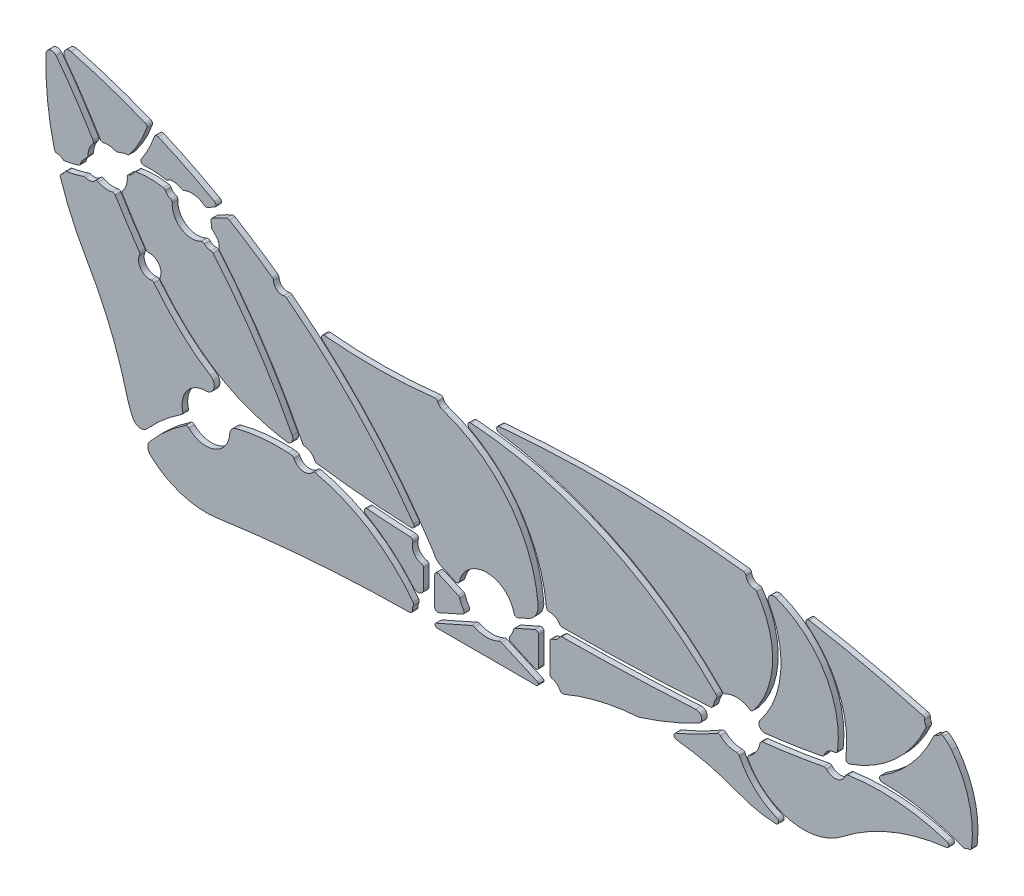
SolidWorks part; units mm, degrees
material "ｴﾎﾟｷｼ樹脂(充填剤なし)"
ref_plane "正面" through (0, 0, 0) normal (0, 0, 1) x (1, 0, 0)
ref_plane "平面" through (0, 0, 0) normal (0, 1, 0) x (1, 0, 0)
ref_plane "右側面" through (0, 0, 0) normal (1, 0, 0) x (0, 0, -1)
sketch "ｽｹｯﾁ1" plane through (0, 0, 0) normal (0, 0, 1) x (1, 0, 0)
  line L1 (22.5, 0.101) -> (22.5, -10.101)
  line L2 (22.5, 0.101) -> (22.5, -10.101)
  line L3 (-22.5, -6.4126) -> (-22.5, 0.101)
  line L4 (-22.5, -6.4126) -> (-22.5, 0.101)
  line L6 (11.119, 1.5832) -> (14.7807, 3.2107)
  line L7 (-17.0939, -10.9558) -> (-8.626, -7.1923)
  line L8 (-18.5, 0.042) -> (-18.5, -10.042)
  line L9 (-10.1663, -2.1231) -> (-17.0939, 0.9558)
  line L10 (-17.0939, -10.9558) -> (-8.626, -7.1923)
  line L11 (-18.5, 0.042) -> (-18.5, -10.042)
  line L12 (-10.1663, -2.1231) -> (-17.0939, 0.9558)
  line L13 (8.626, -7.1923) -> (17.0939, -10.9558)
  line L14 (17.0939, 0.9558) -> (10.1663, -2.1231)
  line L15 (18.5, -10.042) -> (18.5, 0.042)
  line L16 (8.626, -7.1923) -> (17.0939, -10.9558)
  line L17 (17.0939, 0.9558) -> (10.1663, -2.1231)
  line L18 (18.5, -10.042) -> (18.5, 0.042)
  line L19 (-16.2024, 3.8425) -> (-11.119, 1.5832)
  line L20 (11.119, 1.5832) -> (14.7807, 3.2107)
  line L21 (-16.2024, 3.8425) -> (-11.119, 1.5832)
  line L23 (-17.5, -16) -> (17.5, -16)
  line L24 (-5.2366, -8.9688) -> (-17.9339, -14.6121)
  line L25 (17.9339, -14.6121) -> (5.2366, -8.9688)
  line L26 (-17.5, -16) -> (17.5, -16)
  line L27 (-5.2366, -8.9688) -> (-17.9339, -14.6121)
  line L28 (17.9339, -14.6121) -> (5.2366, -8.9688)
  arc A26 (83.2113, 1.2758) -> (89.0603, -0.9998) centre (89, 7.5) ccw
  arc A27 (89.967, -1.5631) -> (89.0603, -0.9998) centre (89.0674, -1.9998) ccw
  arc A28 (89.967, -1.5631) -> (103.3566, -14.0607) centre (112.8701, 9.5532) ccw
  arc A29 (102.9573, -15.9879) -> (103.3566, -14.0607) centre (102.9829, -14.9883) ccw
  arc A30 (90.1176, -13.3365) -> (102.9573, -15.9879) centre (103.9017, 21) ccw
  arc A31 (90.1176, -13.3365) -> (67.6378, -7.8134) centre (59.3978, -89.8605) ccw
  arc A32 (67.3468, -5.898) -> (67.6378, -7.8134) centre (67.7378, -6.8184) ccw
  arc A33 (67.3468, -5.898) -> (82.0317, 1.4104) centre (13.9413, 119.818) ccw
  arc A34 (83.2113, 1.2758) -> (82.0317, 1.4104) centre (82.5302, 0.5435) ccw
  arc A35 (83.2113, 1.2758) -> (89.0603, -0.9998) centre (89, 7.5) ccw
  arc A36 (89.967, -1.5631) -> (89.0603, -0.9998) centre (89.0674, -1.9998) ccw
  arc A37 (89.967, -1.5631) -> (103.3566, -14.0607) centre (112.8701, 9.5532) ccw
  arc A38 (102.9573, -15.9879) -> (103.3566, -14.0607) centre (102.9829, -14.9883) ccw
  arc A39 (90.1176, -13.3365) -> (102.9573, -15.9879) centre (103.9017, 21) ccw
  arc A40 (90.1176, -13.3365) -> (67.6378, -7.8134) centre (59.3978, -89.8605) ccw
  arc A41 (67.3468, -5.898) -> (67.6378, -7.8134) centre (67.7378, -6.8184) ccw
  arc A42 (67.3468, -5.898) -> (82.0317, 1.4104) centre (13.9413, 119.818) ccw
  arc A43 (83.2113, 1.2758) -> (82.0317, 1.4104) centre (82.5302, 0.5435) ccw
  arc A45 (129.2172, 15.4989) -> (156.4002, 40.1644) centre (114.0417, 59.5347) ccw
  arc A46 (127.9008, 16.5808) -> (129.2172, 15.4989) centre (128.8914, 16.4443) ccw
  arc A47 (127.9008, 16.5808) -> (114.0595, 50.8962) centre (91.0356, 21.6602) ccw
  arc A48 (163.9203, 8.9775) -> (128.5572, 11.8079) centre (140.2604, -64.3004) ccw
  arc A49 (163.7257, 7.0322) -> (163.9203, 8.9775) centre (163.613, 8.0259) ccw
  arc A50 (163.7257, 7.0322) -> (126.7209, -8.1253) centre (172, -65.9175) ccw
  arc A51 (93.0844, -1.0722) -> (126.7209, -8.1253) centre (112.8701, 9.5532) ccw
  arc A52 (93.4427, 0.2535) -> (93.0844, -1.0722) centre (93.9654, -0.5991) ccw
  arc A53 (93.4427, 0.2535) -> (97.3718, 6.0294) centre (89, 7.5) ccw
  arc A54 (98.2474, 6.8503) -> (97.3718, 6.0294) centre (98.3567, 5.8563) ccw
  arc A55 (98.2474, 6.8503) -> (120.0633, 10.1693) centre (69.0994, 271.8045) ccw
  arc A56 (121.0036, 9.8502) -> (120.0633, 10.1693) centre (120.2545, 9.1877) ccw
  arc A57 (121.0036, 9.8502) -> (127.7673, 11.1556) centre (124, 12.5) ccw
  arc A58 (128.5572, 11.8079) -> (127.7673, 11.1556) centre (128.7091, 10.8195) ccw
  arc A59 (163.9203, 8.9775) -> (128.5572, 11.8079) centre (140.2604, -64.3004) ccw
  arc A60 (163.7257, 7.0322) -> (163.9203, 8.9775) centre (163.613, 8.0259) ccw
  arc A61 (163.7257, 7.0322) -> (126.7209, -8.1253) centre (172, -65.9175) ccw
  arc A62 (93.0844, -1.0722) -> (126.7209, -8.1253) centre (112.8701, 9.5532) ccw
  arc A63 (93.4427, 0.2535) -> (93.0844, -1.0722) centre (93.9654, -0.5991) ccw
  arc A64 (93.4427, 0.2535) -> (97.3718, 6.0294) centre (89, 7.5) ccw
  arc A65 (98.2474, 6.8503) -> (97.3718, 6.0294) centre (98.3567, 5.8563) ccw
  arc A66 (98.2474, 6.8503) -> (120.0633, 10.1693) centre (69.0994, 271.8045) ccw
  arc A67 (121.0036, 9.8502) -> (120.0633, 10.1693) centre (120.2545, 9.1877) ccw
  arc A68 (121.0036, 9.8502) -> (127.7673, 11.1556) centre (124, 12.5) ccw
  arc A69 (128.5572, 11.8079) -> (127.7673, 11.1556) centre (128.7091, 10.8195) ccw
  arc A70 (114.85, 52.6669) -> (114.0595, 50.8962) centre (114.6782, 51.6818) ccw
  arc A71 (155.2686, 43.5545) -> (114.85, 52.6669) centre (42.29, -363.3692) ccw
  arc A72 (156.0008, 42.5682) -> (155.2686, 43.5545) centre (155.001, 42.5909) ccw
  arc A73 (156.0008, 42.5682) -> (156.3681, 41.0602) centre (159, 42.5) ccw
  arc A74 (156.4002, 40.1644) -> (156.3681, 41.0602) centre (155.4908, 40.5803) ccw
  arc A75 (129.2172, 15.4989) -> (156.4002, 40.1644) centre (114.0417, 59.5347) ccw
  arc A76 (127.9008, 16.5808) -> (129.2172, 15.4989) centre (128.8914, 16.4443) ccw
  arc A77 (127.9008, 16.5808) -> (114.0595, 50.8962) centre (91.0356, 21.6602) ccw
  arc A78 (114.85, 52.6669) -> (114.0595, 50.8962) centre (114.6782, 51.6818) ccw
  arc A79 (155.2686, 43.5545) -> (114.85, 52.6669) centre (42.29, -363.3692) ccw
  arc A80 (156.0008, 42.5682) -> (155.2686, 43.5545) centre (155.001, 42.5909) ccw
  arc A81 (156.0008, 42.5682) -> (156.3681, 41.0602) centre (159, 42.5) ccw
  arc A82 (156.4002, 40.1644) -> (156.3681, 41.0602) centre (155.4908, 40.5803) ccw
  arc A83 (97.4246, 13.2154) -> (99.214, 9.978) centre (98.9855, 11.9649) ccw
  arc A84 (97.4246, 13.2154) -> (100.5051, 50.879) centre (71.0713, 34.3286) ccw
  arc A85 (93.5868, 14.6562) -> (85.0963, 15.0506) centre (89, 7.5) ccw
  arc A86 (171.786, 10.4924) -> (170.5639, 10.1339) centre (172, 7.5) ccw
  arc A87 (169.717, 10.0822) -> (170.5639, 10.1339) centre (170.0852, 11.0119) ccw
  arc A88 (169.717, 10.0822) -> (140.9263, 15.6997) centre (140.2604, -64.3004) ccw
  arc A89 (140.4029, 17.5466) -> (140.9263, 15.6997) centre (140.9346, 16.6997) ccw
  arc A90 (140.4029, 17.5466) -> (159.198, 39.0695) centre (114.0417, 59.5347) ccw
  arc A91 (159.8316, 39.6176) -> (159.198, 39.0695) centre (160.1088, 38.6568) ccw
  arc A92 (159.8316, 39.6176) -> (161.317, 40.5944) centre (159, 42.5) ccw
  arc A93 (162.6526, 40.7855) -> (161.317, 40.5944) centre (162.0894, 39.9592) ccw
  arc A94 (165.6353, 37.9447) -> (162.6526, 40.7855) centre (155.4945, 30.2837) ccw
  arc A95 (172.7066, 11.3632) -> (165.6353, 37.9447) centre (136.5587, 15.9784) ccw
  arc A96 (171.786, 10.4924) -> (172.7066, 11.3632) centre (171.7146, 11.4898) ccw
  arc A97 (171.786, 10.4924) -> (170.5639, 10.1339) centre (172, 7.5) ccw
  arc A98 (169.717, 10.0822) -> (170.5639, 10.1339) centre (170.0852, 11.0119) ccw
  arc A99 (169.717, 10.0822) -> (140.9263, 15.6997) centre (140.2604, -64.3004) ccw
  arc A100 (140.4029, 17.5466) -> (140.9263, 15.6997) centre (140.9346, 16.6997) ccw
  arc A101 (140.4029, 17.5466) -> (159.198, 39.0695) centre (114.0417, 59.5347) ccw
  arc A102 (159.8316, 39.6176) -> (159.198, 39.0695) centre (160.1088, 38.6568) ccw
  arc A103 (159.8316, 39.6176) -> (161.317, 40.5944) centre (159, 42.5) ccw
  arc A104 (162.6526, 40.7855) -> (161.317, 40.5944) centre (162.0894, 39.9592) ccw
  arc A105 (165.6353, 37.9447) -> (162.6526, 40.7855) centre (155.4945, 30.2837) ccw
  arc A106 (172.7066, 11.3632) -> (165.6353, 37.9447) centre (136.5587, 15.9784) ccw
  arc A107 (171.786, 10.4924) -> (172.7066, 11.3632) centre (171.7146, 11.4898) ccw
  arc A108 (83.9236, 15.238) -> (85.0963, 15.0506) centre (84.637, 15.9389) ccw
  arc A109 (83.9236, 15.238) -> (4.4224, 55.2639) centre (-14.6672, -81.6202) ccw
  arc A110 (4.471, 57.2503) -> (4.4224, 55.2639) centre (4.5606, 56.2543) ccw
  arc A111 (91.4838, 56.0721) -> (4.471, 57.2503) centre (42.29, -363.3692) ccw
  arc A112 (92.3587, 55.2099) -> (91.4838, 56.0721) centre (91.3673, 55.0789) ccw
  arc A113 (92.3587, 55.2099) -> (95.319, 52.6028) centre (95.3328, 55.6027) ccw
  arc A114 (96.1287, 52.1831) -> (95.319, 52.6028) centre (95.3143, 51.6028) ccw
  arc A115 (94.9009, 14.8656) -> (96.1287, 52.1831) centre (71.0713, 34.3286) ccw
  arc A116 (93.5868, 14.6562) -> (94.9009, 14.8656) centre (94.1264, 15.4981) ccw
  arc A117 (93.5868, 14.6562) -> (85.0963, 15.0506) centre (89, 7.5) ccw
  arc A118 (83.9236, 15.238) -> (85.0963, 15.0506) centre (84.637, 15.9389) ccw
  arc A119 (83.9236, 15.238) -> (4.4224, 55.2639) centre (-14.6672, -81.6202) ccw
  arc A120 (4.471, 57.2503) -> (4.4224, 55.2639) centre (4.5606, 56.2543) ccw
  arc A121 (91.4838, 56.0721) -> (4.471, 57.2503) centre (42.29, -363.3692) ccw
  arc A122 (92.3587, 55.2099) -> (91.4838, 56.0721) centre (91.3673, 55.0789) ccw
  arc A123 (92.3587, 55.2099) -> (95.319, 52.6028) centre (95.3328, 55.6027) ccw
  arc A124 (96.1287, 52.1831) -> (95.319, 52.6028) centre (95.3143, 51.6028) ccw
  arc A125 (94.9009, 14.8656) -> (96.1287, 52.1831) centre (71.0713, 34.3286) ccw
  arc A126 (93.5868, 14.6562) -> (94.9009, 14.8656) centre (94.1264, 15.4981) ccw
  arc A127 (81.6673, 13.2539) -> (-5.6096, 53.2849) centre (-14.6672, -81.6202) ccw
  arc A128 (81.8017, 12.0204) -> (81.6673, 13.2539) centre (80.9548, 12.5522) ccw
  arc A129 (81.8017, 12.0204) -> (80.6633, 9.158) centre (89, 7.5) ccw
  arc A130 (79.7472, 8.3552) -> (80.6633, 9.158) centre (79.6825, 9.3531) ccw
  arc A131 (26.8289, 6.5106) -> (79.7472, 8.3552) centre (22.5, 890.7) ccw
  arc A132 (25.9592, 7.0085) -> (26.8289, 6.5106) centre (26.824, 7.5106) ccw
  arc A133 (25.9592, 7.0085) -> (22.314, 8.9957) centre (22.5, 5) ccw
  arc A134 (21.2718, 9.9017) -> (22.314, 8.9957) centre (22.2675, 9.9946) ccw
  arc A135 (21.2718, 9.9017) -> (-6.1525, 51.4076) centre (-31.2679, 5) ccw
  arc A136 (-5.6096, 53.2849) -> (-6.1525, 51.4076) centre (-5.6766, 52.2871) ccw
  arc A137 (81.6673, 13.2539) -> (-5.6096, 53.2849) centre (-14.6672, -81.6202) ccw
  arc A138 (81.8017, 12.0204) -> (81.6673, 13.2539) centre (80.9548, 12.5522) ccw
  arc A139 (81.8017, 12.0204) -> (80.6633, 9.158) centre (89, 7.5) ccw
  arc A140 (79.7472, 8.3552) -> (80.6633, 9.158) centre (79.6825, 9.3531) ccw
  arc A141 (26.8289, 6.5106) -> (79.7472, 8.3552) centre (22.5, 890.7) ccw
  arc A142 (25.9592, 7.0085) -> (26.8289, 6.5106) centre (26.824, 7.5106) ccw
  arc A143 (25.9592, 7.0085) -> (22.314, 8.9957) centre (22.5, 5) ccw
  arc A144 (21.2718, 9.9017) -> (22.314, 8.9957) centre (22.2675, 9.9946) ccw
  arc A145 (21.2718, 9.9017) -> (-6.1525, 51.4076) centre (-31.2679, 5) ccw
  arc A146 (-5.6096, 53.2849) -> (-6.1525, 51.4076) centre (-5.6766, 52.2871) ccw
  arc A147 (102.9446, 53.7342) -> (100.5051, 50.879) centre (102.2484, 51.8592) ccw
  arc A148 (23.3, 1.0808) -> (25.969, 3.0085) centre (22.5, 5) ccw
  arc A149 (26.8313, 3.5106) -> (25.969, 3.0085) centre (26.8362, 2.5106) ccw
  arc A150 (26.8313, 3.5106) -> (74.4485, 5.0222) centre (22.5, 890.7) ccw
  arc A151 (75.487, 1.2505) -> (74.4485, 5.0222) centre (74.5656, 3.0256) ccw
  arc A152 (54.3014, -7.5287) -> (75.487, 1.2505) centre (13.9413, 119.818) ccw
  arc A153 (54.0639, -7.5734) -> (54.3014, -7.5287) centre (53.9993, -6.5755) ccw
  arc A154 (54.0639, -7.5734) -> (27.4366, -13.8466) centre (59.3978, -89.8605) ccw
  arc A155 (26.1392, -13.3399) -> (27.4366, -13.8466) centre (27.049, -12.9248) ccw
  arc A156 (26.1392, -13.3399) -> (23.3, -11.0808) centre (22.5, -15) ccw
  arc A157 (22.5, -10.101) -> (23.3, -11.0808) centre (23.5, -10.101) ccw
  arc A158 (23.3, 1.0808) -> (22.5, 0.101) centre (23.5, 0.101) ccw
  arc A159 (23.3, 1.0808) -> (25.969, 3.0085) centre (22.5, 5) ccw
  arc A160 (26.8313, 3.5106) -> (25.969, 3.0085) centre (26.8362, 2.5106) ccw
  arc A161 (26.8313, 3.5106) -> (74.4485, 5.0222) centre (22.5, 890.7) ccw
  arc A162 (75.487, 1.2505) -> (74.4485, 5.0222) centre (74.5656, 3.0256) ccw
  arc A163 (54.3014, -7.5287) -> (75.487, 1.2505) centre (13.9413, 119.818) ccw
  arc A164 (54.0639, -7.5734) -> (54.3014, -7.5287) centre (53.9993, -6.5755) ccw
  arc A165 (54.0639, -7.5734) -> (27.4366, -13.8466) centre (59.3978, -89.8605) ccw
  arc A166 (26.1392, -13.3399) -> (27.4366, -13.8466) centre (27.049, -12.9248) ccw
  arc A167 (26.1392, -13.3399) -> (23.3, -11.0808) centre (22.5, -15) ccw
  arc A168 (22.5, -10.101) -> (23.3, -11.0808) centre (23.5, -10.101) ccw
  arc A169 (23.3, 1.0808) -> (22.5, 0.101) centre (23.5, 0.101) ccw
  arc A170 (124.9796, 17.3747) -> (102.9446, 53.7342) centre (91.0356, 21.6602) ccw
  arc A171 (123.99, 16.5) -> (124.9796, 17.3747) centre (123.9875, 17.5) ccw
  arc A172 (123.99, 16.5) -> (120.207, 13.7702) centre (124, 12.5) ccw
  arc A179 (119.4498, 13.1062) -> (120.207, 13.7702) centre (119.2588, 14.0878) ccw
  arc A180 (99.214, 9.978) -> (119.4498, 13.1062) centre (69.0994, 271.8045) ccw
  arc A181 (97.4246, 13.2154) -> (99.214, 9.978) centre (98.9855, 11.9649) ccw
  arc A182 (97.4246, 13.2154) -> (100.5051, 50.879) centre (71.0713, 34.3286) ccw
  arc A183 (102.9446, 53.7342) -> (100.5051, 50.879) centre (102.2484, 51.8592) ccw
  arc A184 (124.9796, 17.3747) -> (102.9446, 53.7342) centre (91.0356, 21.6602) ccw
  arc A185 (123.99, 16.5) -> (124.9796, 17.3747) centre (123.9875, 17.5) ccw
  arc A186 (123.99, 16.5) -> (120.207, 13.7702) centre (124, 12.5) ccw
  arc A187 (119.4498, 13.1062) -> (120.207, 13.7702) centre (119.2588, 14.0878) ccw
  arc A188 (99.214, 9.978) -> (119.4498, 13.1062) centre (69.0994, 271.8045) ccw
  arc A196 (-9.6113, -2.7608) -> (-8.2111, -5.7077) centre (0, 0) ccw
  arc A197 (-8.626, -7.1923) -> (-8.2111, -5.7077) centre (-9.0322, -6.2785) ccw
  arc A198 (-26.3403, 6.1191) -> (-23.3, 1.0808) centre (-22.5, 5) ccw
  arc A199 (-22.5, 0.101) -> (-23.3, 1.0808) centre (-23.5, 0.101) ccw
  arc A200 (-26.0294, -7.7013) -> (-22.5, -6.4126) centre (-24.5, -6.4126) ccw
  arc A201 (-150.204, 61.7869) -> (-145.3266, 62.9598) centre (-156.5, 98.6967) ccw
  arc A202 (-151.0229, 62.0134) -> (-150.204, 61.7869) centre (-150.3722, 62.7727) ccw
  arc A203 (-151.0229, 62.0134) -> (-152.9962, 62.7355) centre (-152.9752, 59.7355) ccw
  arc A204 (-153.9743, 63.4967) -> (-152.9962, 62.7355) centre (-153.0032, 63.7354) ccw
  arc A205 (-156.9544, 91.5668) -> (-153.9743, 63.4967) centre (-52.35, 88.479) ccw
  arc A206 (-153.3792, 92.7391) -> (-156.9544, 91.5668) centre (-154.9553, 91.5078) ccw
  arc A207 (-140.2901, 72.0654) -> (-140.1936, 73.2435) centre (-141.0458, 72.7203) ccw
  arc A208 (-92.6465, 72.9722) -> (-97.7506, 70.3671) centre (-65, 12.5) ccw
  arc A209 (-91.7165, 72.9204) -> (-92.6465, 72.9722) centre (-92.2307, 72.0627) ccw
  arc A210 (-76.3493, 62.7985) -> (-91.7165, 72.9204) centre (-203.2901, -113.1988) ccw
  arc A211 (-75.9352, 62.0305) -> (-76.3493, 62.7985) centre (-76.9343, 61.9874) ccw
  arc A212 (-75.9352, 62.0305) -> (-72.1979, 59.2524) centre (-72.938, 62.1596) ccw
  arc A213 (-71.3431, 59.0772) -> (-72.1979, 59.2524) centre (-71.9512, 58.2833) ccw
  arc A214 (-26.022, 11.9612) -> (-71.3431, 59.0772) centre (-203.2901, -113.1988) ccw
  arc A215 (-26.8783, 10.3852) -> (-26.022, 11.9612) centre (-26.8389, 11.3844) ccw
  arc A216 (-60.4936, 13.364) -> (-26.8783, 10.3852) centre (-13.2682, 355.1295) ccw
  arc A217 (-61.2853, 13.9837) -> (-60.4936, 13.364) centre (-60.3567, 14.3546) ccw
  arc A218 (-61.2853, 13.9837) -> (-64.7539, 16.4924) centre (-65, 12.5) ccw
  arc A219 (-65.5834, 17.0366) -> (-64.7539, 16.4924) centre (-64.6924, 17.4905) ccw
  arc A220 (-65.5834, 17.0366) -> (-95.1344, 61.7139) centre (-276.8279, -90.5756) ccw
  arc A221 (-95.3497, 62.5466) -> (-95.1344, 61.7139) centre (-94.368, 62.3562) ccw
  arc A222 (-95.3497, 62.5466) -> (-96.0213, 65.0748) centre (-98.2949, 63.1176) ccw
  arc A223 (-96.0213, 65.0748) -> (-97.7054, 66.8832) centre (-120, 44.4324) ccw
  arc A224 (-98.0007, 67.5789) -> (-97.7054, 66.8832) centre (-97.0008, 67.5928) ccw
  arc A225 (-98.0007, 67.5789) -> (-98.2258, 69.2449) centre (-105, 67.4812) ccw
  arc A226 (-97.7506, 70.3671) -> (-98.2258, 69.2449) centre (-97.2581, 69.4969) ccw
  arc A227 (-92.6465, 72.9722) -> (-97.7506, 70.3671) centre (-65, 12.5) ccw
  arc A228 (-91.7165, 72.9204) -> (-92.6465, 72.9722) centre (-92.2307, 72.0627) ccw
  arc A229 (-76.3493, 62.7985) -> (-91.7165, 72.9204) centre (-203.2901, -113.1988) ccw
  arc A230 (-75.9352, 62.0305) -> (-76.3493, 62.7985) centre (-76.9343, 61.9874) ccw
  arc A231 (-75.9352, 62.0305) -> (-72.1979, 59.2524) centre (-72.938, 62.1596) ccw
  arc A232 (-71.3431, 59.0772) -> (-72.1979, 59.2524) centre (-71.9512, 58.2833) ccw
  arc A233 (-26.022, 11.9612) -> (-71.3431, 59.0772) centre (-203.2901, -113.1988) ccw
  arc A234 (-26.8783, 10.3852) -> (-26.022, 11.9612) centre (-26.8389, 11.3844) ccw
  arc A235 (-60.4936, 13.364) -> (-26.8783, 10.3852) centre (-13.2682, 355.1295) ccw
  arc A236 (-61.2853, 13.9837) -> (-60.4936, 13.364) centre (-60.3567, 14.3546) ccw
  arc A237 (-61.2853, 13.9837) -> (-64.7539, 16.4924) centre (-65, 12.5) ccw
  arc A238 (-65.5834, 17.0366) -> (-64.7539, 16.4924) centre (-64.6924, 17.4905) ccw
  arc A239 (-65.5834, 17.0366) -> (-95.1344, 61.7139) centre (-276.8279, -90.5756) ccw
  arc A240 (-95.3497, 62.5466) -> (-95.1344, 61.7139) centre (-94.368, 62.3562) ccw
  arc A241 (-95.3497, 62.5466) -> (-96.0213, 65.0748) centre (-98.2949, 63.1176) ccw
  arc A242 (-96.0213, 65.0748) -> (-97.7054, 66.8832) centre (-120, 44.4324) ccw
  arc A243 (-98.0007, 67.5789) -> (-97.7054, 66.8832) centre (-97.0008, 67.5928) ccw
  arc A244 (-98.0007, 67.5789) -> (-98.2258, 69.2449) centre (-105, 67.4812) ccw
  arc A245 (-97.7506, 70.3671) -> (-98.2258, 69.2449) centre (-97.2581, 69.4969) ccw
  arc A246 (-140.2901, 72.0654) -> (-141.9993, 67.5789) centre (-135, 67.4812) ccw
  arc A247 (-142.2946, 66.8832) -> (-141.9993, 67.5789) centre (-142.9992, 67.5928) ccw
  arc A248 (-142.2946, 66.8832) -> (-143.9787, 65.0748) centre (-120, 44.4324) ccw
  arc A249 (-143.9787, 65.0748) -> (-144.645, 63.7151) centre (-141.7051, 63.1176) ccw
  arc A250 (-145.3266, 62.9598) -> (-144.645, 63.7151) centre (-145.625, 63.9142) ccw
  arc A251 (-150.204, 61.7869) -> (-145.3266, 62.9598) centre (-156.5, 98.6967) ccw
  arc A252 (-151.0229, 62.0134) -> (-150.204, 61.7869) centre (-150.3722, 62.7727) ccw
  arc A253 (-151.0229, 62.0134) -> (-152.9962, 62.7355) centre (-152.9752, 59.7355) ccw
  arc A254 (-153.9743, 63.4967) -> (-152.9962, 62.7355) centre (-153.0032, 63.7354) ccw
  arc A255 (-156.9544, 91.5668) -> (-153.9743, 63.4967) centre (-52.35, 88.479) ccw
  arc A256 (-153.3792, 92.7391) -> (-156.9544, 91.5668) centre (-154.9553, 91.5078) ccw
  arc A257 (-140.2901, 72.0654) -> (-140.1936, 73.2435) centre (-141.0458, 72.7203) ccw
  arc A258 (-140.2901, 72.0654) -> (-141.9993, 67.5789) centre (-135, 67.4812) ccw
  arc A259 (-142.2946, 66.8832) -> (-141.9993, 67.5789) centre (-142.9992, 67.5928) ccw
  arc A260 (-142.2946, 66.8832) -> (-143.9787, 65.0748) centre (-120, 44.4324) ccw
  arc A261 (-143.9787, 65.0748) -> (-144.645, 63.7151) centre (-141.7051, 63.1176) ccw
  arc A262 (-145.3266, 62.9598) -> (-144.645, 63.7151) centre (-145.625, 63.9142) ccw
  arc A263 (-26.0294, -7.7013) -> (-43.0938, 6.4818) centre (-74.1755, -48.2713) ccw
  arc A264 (-42.5161, 8.3479) -> (-43.0938, 6.4818) centre (-42.6001, 7.3514) ccw
  arc A265 (-42.5161, 8.3479) -> (-27.2601, 7.398) centre (-13.2682, 355.1295) ccw
  arc A266 (-122.9876, 76.0572) -> (-118.3344, 85.3171) centre (-156.5, 98.6967) ccw
  arc A267 (-116.993, 85.9037) -> (-118.3344, 85.3171) centre (-117.3907, 84.9862) ccw
  arc A268 (-96.9469, 75.9576) -> (-116.993, 85.9037) centre (-203.2901, -113.1988) ccw
  arc A269 (-96.9768, 74.198) -> (-96.9469, 75.9576) centre (-97.4369, 75.0859) ccw
  arc A270 (-96.9768, 74.198) -> (-99.4771, 72.8365) centre (-65, 12.5) ccw
  arc A271 (-100.6016, 72.9268) -> (-99.4771, 72.8365) centre (-99.9733, 73.7047) ccw
  arc A272 (-100.6016, 72.9268) -> (-107.7452, 73.9205) centre (-105, 67.4812) ccw
  arc A273 (-108.5008, 73.9088) -> (-107.7452, 73.9205) centre (-108.1373, 74.8404) ccw
  arc A274 (-108.5008, 73.9088) -> (-110.8362, 74.7163) centre (-120, 44.4324) ccw
  arc A275 (-110.8362, 74.7163) -> (-113.5331, 74.2236) centre (-111.7051, 71.8449) ccw
  arc A276 (-114.3306, 74.0344) -> (-113.5331, 74.2236) centre (-114.1425, 75.0165) ccw
  arc A277 (-114.3306, 74.0344) -> (-122.0896, 74.4999) centre (-120, 44.4324) ccw
  arc A278 (-122.9876, 76.0572) -> (-122.0896, 74.4999) centre (-122.1589, 75.4974) ccw
  arc A279 (-122.9876, 76.0572) -> (-118.3344, 85.3171) centre (-156.5, 98.6967) ccw
  arc A280 (-116.993, 85.9037) -> (-118.3344, 85.3171) centre (-117.3907, 84.9862) ccw
  arc A281 (-96.9469, 75.9576) -> (-116.993, 85.9037) centre (-203.2901, -113.1988) ccw
  arc A282 (-96.9768, 74.198) -> (-96.9469, 75.9576) centre (-97.4369, 75.0859) ccw
  arc A283 (-96.9768, 74.198) -> (-99.4771, 72.8365) centre (-65, 12.5) ccw
  arc A284 (-100.6016, 72.9268) -> (-99.4771, 72.8365) centre (-99.9733, 73.7047) ccw
  arc A285 (-100.6016, 72.9268) -> (-107.7452, 73.9205) centre (-105, 67.4812) ccw
  arc A286 (-108.5008, 73.9088) -> (-107.7452, 73.9205) centre (-108.1373, 74.8404) ccw
  arc A287 (-108.5008, 73.9088) -> (-110.8362, 74.7163) centre (-120, 44.4324) ccw
  arc A288 (-110.8362, 74.7163) -> (-113.5331, 74.2236) centre (-111.7051, 71.8449) ccw
  arc A289 (-114.3306, 74.0344) -> (-113.5331, 74.2236) centre (-114.1425, 75.0165) ccw
  arc A290 (-114.3306, 74.0344) -> (-122.0896, 74.4999) centre (-120, 44.4324) ccw
  arc A291 (-122.9876, 76.0572) -> (-122.0896, 74.4999) centre (-122.1589, 75.4974) ccw
  arc A292 (-26.3403, 6.1191) -> (-27.2601, 7.398) centre (-27.3003, 6.3988) ccw
  arc A293 (-26.3403, 6.1191) -> (-23.3, 1.0808) centre (-22.5, 5) ccw
  arc A294 (-22.5, 0.101) -> (-23.3, 1.0808) centre (-23.5, 0.101) ccw
  arc A295 (-26.0294, -7.7013) -> (-22.5, -6.4126) centre (-24.5, -6.4126) ccw
  arc A296 (-106.0705, 1.5503) -> (-91.5134, 7.0221) centre (-100, 7.5) ccw
  arc A297 (-89.2736, 9.7568) -> (-91.5134, 7.0221) centre (-88.5182, 6.8535) ccw
  arc A298 (-70.6226, 11.5834) -> (-89.2736, 9.7568) centre (-74.1755, -48.2713) ccw
  arc A299 (-70.5449, 11.5758) -> (-70.6226, 11.5834) centre (-70.6819, 10.5852) ccw
  arc A300 (-70.5449, 11.5758) -> (-69.4318, 11.4299) centre (-59.6347, 90.4932) ccw
  arc A301 (-68.6438, 10.85) -> (-69.4318, 11.4299) centre (-69.5548, 10.4374) ccw
  arc A302 (-68.6438, 10.85) -> (-61.9641, 9.8955) centre (-65, 12.5) ccw
  arc A303 (-60.9851, 10.2199) -> (-61.9641, 9.8955) centre (-61.2051, 9.2444) ccw
  arc A304 (-26.225, -12.2719) -> (-60.9851, 10.2199) centre (-74.1755, -48.2713) ccw
  arc A305 (-26.1198, -13.2978) -> (-26.225, -12.2719) centre (-27.0247, -12.8723) ccw
  arc A306 (-26.1198, -13.2978) -> (-26.5, -15.0192) centre (-22.5, -15) ccw
  arc A307 (-27.4903, -16.024) -> (-26.5, -15.0192) centre (-27.4999, -15.024) ccw
  arc A308 (-27.4903, -16.024) -> (-95.9045, -21.2094) centre (-22.5, -535.7727) ccw
  arc A309 (-119.7512, -13.7341) -> (-95.9045, -21.2094) centre (-100, 7.5) ccw
  arc A310 (-120.0008, -9.6028) -> (-119.7512, -13.7341) centre (-117.708, -11.5375) ccw
  arc A311 (-107.3377, 1.6835) -> (-120.0008, -9.6028) centre (-74.1755, -48.2713) ccw
  arc A312 (-106.0705, 1.5503) -> (-107.3377, 1.6835) centre (-106.7847, 0.8503) ccw
  arc A313 (-106.0705, 1.5503) -> (-91.5134, 7.0221) centre (-100, 7.5) ccw
  arc A314 (-89.2736, 9.7568) -> (-91.5134, 7.0221) centre (-88.5182, 6.8535) ccw
  arc A315 (-70.6226, 11.5834) -> (-89.2736, 9.7568) centre (-74.1755, -48.2713) ccw
  arc A316 (-70.5449, 11.5758) -> (-70.6226, 11.5834) centre (-70.6819, 10.5852) ccw
  arc A317 (-70.5449, 11.5758) -> (-69.4318, 11.4299) centre (-59.6347, 90.4932) ccw
  arc A318 (-68.6438, 10.85) -> (-69.4318, 11.4299) centre (-69.5548, 10.4374) ccw
  arc A319 (-68.6438, 10.85) -> (-61.9641, 9.8955) centre (-65, 12.5) ccw
  arc A320 (-60.9851, 10.2199) -> (-61.9641, 9.8955) centre (-61.2051, 9.2444) ccw
  arc A321 (-26.225, -12.2719) -> (-60.9851, 10.2199) centre (-74.1755, -48.2713) ccw
  arc A322 (-26.1198, -13.2978) -> (-26.225, -12.2719) centre (-27.0247, -12.8723) ccw
  arc A323 (-26.1198, -13.2978) -> (-26.5, -15.0192) centre (-22.5, -15) ccw
  arc A324 (-27.4903, -16.024) -> (-26.5, -15.0192) centre (-27.4999, -15.024) ccw
  arc A325 (-27.4903, -16.024) -> (-95.9045, -21.2094) centre (-22.5, -535.7727) ccw
  arc A326 (-119.7512, -13.7341) -> (-95.9045, -21.2094) centre (-100, 7.5) ccw
  arc A327 (-120.0008, -9.6028) -> (-119.7512, -13.7341) centre (-117.708, -11.5375) ccw
  arc A328 (-107.3377, 1.6835) -> (-120.0008, -9.6028) centre (-74.1755, -48.2713) ccw
  arc A329 (-106.0705, 1.5503) -> (-107.3377, 1.6835) centre (-106.7847, 0.8503) ccw
  arc A330 (-26.0294, -7.7013) -> (-43.0938, 6.4818) centre (-74.1755, -48.2713) ccw
  arc A331 (-42.5161, 8.3479) -> (-43.0938, 6.4818) centre (-42.6001, 7.3514) ccw
  arc A332 (-42.5161, 8.3479) -> (-27.2601, 7.398) centre (-13.2682, 355.1295) ccw
  arc A333 (-26.3403, 6.1191) -> (-27.2601, 7.398) centre (-27.3003, 6.3988) ccw
  arc A334 (-18.5, -10.042) -> (-17.0939, -10.9558) centre (-17.5, -10.042) ccw
  arc A335 (-17.0939, 0.9558) -> (-18.5, 0.042) centre (-17.5, 0.042) ccw
  arc A336 (-9.6113, -2.7608) -> (-10.1663, -2.1231) centre (-10.5725, -3.0369) ccw
  arc A337 (-148.0871, 96.6622) -> (-150.1845, 93.5129) centre (-148.5959, 94.728) ccw
  arc A338 (-121.6343, 87.8518) -> (-148.0871, 96.6622) centre (-203.2901, -113.1988) ccw
  arc A339 (-121.0642, 86.6023) -> (-121.6343, 87.8518) centre (-122.0106, 86.9253) ccw
  arc A340 (-127.3364, 75.2137) -> (-121.0642, 86.6023) centre (-156.5, 98.6967) ccw
  arc A341 (-128.1602, 74.8418) -> (-127.3364, 75.2137) centre (-128.1152, 75.8408) ccw
  arc A342 (-128.1602, 74.8418) -> (-129.1638, 74.7163) centre (-128.2949, 71.8449) ccw
  arc A343 (-129.1638, 74.7163) -> (-131.4992, 73.9088) centre (-120, 44.4324) ccw
  arc A344 (-132.2548, 73.9205) -> (-131.4992, 73.9088) centre (-131.8627, 74.8404) ccw
  arc A345 (-100.5079, 61.0921) -> (-98.2079, 60.1189) centre (-98.2949, 63.1176) ccw
  arc A346 (-97.4124, 59.7615) -> (-98.2079, 60.1189) centre (-98.1789, 59.1193) ccw
  arc A347 (-69.2612, 17.6244) -> (-97.4124, 59.7615) centre (-276.8279, -90.5756) ccw
  arc A348 (-71.3386, 14.7231) -> (-69.2612, 17.6244) centre (-71.0347, 16.6999) ccw
  arc A349 (-116.2864, 42.9461) -> (-116.1386, 41.9495) centre (-115.358, 42.5745) ccw
  arc A350 (-116.2864, 42.9461) -> (-120.3745, 48.4148) centre (-120, 44.4324) ccw
  arc A351 (-121.2864, 48.8356) -> (-120.3745, 48.4148) centre (-120.4681, 49.4104) ccw
  arc A352 (-129.6405, 62.9784) -> (-129.7265, 61.811) centre (-128.8749, 62.3351) ccw
  arc A353 (-129.6405, 62.9784) -> (-128.0179, 67.9818) centre (-135, 67.4812) ccw
  arc A354 (-127.3391, 69.0012) -> (-128.0179, 67.9818) centre (-127.0205, 68.0533) ccw
  arc A355 (-127.3391, 69.0012) -> (-125.5769, 70.575) centre (-128.2949, 71.8449) ccw
  arc A356 (-124.8496, 71.1356) -> (-125.5769, 70.575) centre (-124.6709, 70.1517) ccw
  arc A357 (-115.1504, 71.1356) -> (-124.8496, 71.1356) centre (-120, 44.4324) ccw
  arc A358 (-114.4231, 70.575) -> (-115.1504, 71.1356) centre (-115.3291, 70.1517) ccw
  arc A359 (-114.4231, 70.575) -> (-112.6609, 69.0012) centre (-111.7051, 71.8449) ccw
  arc A360 (-111.9821, 67.9818) -> (-112.6609, 69.0012) centre (-112.9795, 68.0533) ccw
  arc A361 (-111.9821, 67.9818) -> (-101.7149, 61.3) centre (-105, 67.4812) ccw
  arc A362 (-100.5079, 61.0921) -> (-101.7149, 61.3) centre (-101.2456, 60.4169) ccw
  arc A363 (-100.5079, 61.0921) -> (-98.2079, 60.1189) centre (-98.2949, 63.1176) ccw
  arc A364 (-97.4124, 59.7615) -> (-98.2079, 60.1189) centre (-98.1789, 59.1193) ccw
  arc A365 (-69.2612, 17.6244) -> (-97.4124, 59.7615) centre (-276.8279, -90.5756) ccw
  arc A366 (-71.3386, 14.7231) -> (-69.2612, 17.6244) centre (-71.0347, 16.6999) ccw
  arc A367 (-116.2864, 42.9461) -> (-116.1386, 41.9495) centre (-115.358, 42.5745) ccw
  arc A368 (-116.2864, 42.9461) -> (-120.3745, 48.4148) centre (-120, 44.4324) ccw
  arc A369 (-121.2864, 48.8356) -> (-120.3745, 48.4148) centre (-120.4681, 49.4104) ccw
  arc A370 (-129.6405, 62.9784) -> (-129.7265, 61.811) centre (-128.8749, 62.3351) ccw
  arc A371 (-129.6405, 62.9784) -> (-128.0179, 67.9818) centre (-135, 67.4812) ccw
  arc A372 (-127.3391, 69.0012) -> (-128.0179, 67.9818) centre (-127.0205, 68.0533) ccw
  arc A373 (-127.3391, 69.0012) -> (-125.5769, 70.575) centre (-128.2949, 71.8449) ccw
  arc A374 (-124.8496, 71.1356) -> (-125.5769, 70.575) centre (-124.6709, 70.1517) ccw
  arc A375 (-115.1504, 71.1356) -> (-124.8496, 71.1356) centre (-120, 44.4324) ccw
  arc A376 (-114.4231, 70.575) -> (-115.1504, 71.1356) centre (-115.3291, 70.1517) ccw
  arc A377 (-114.4231, 70.575) -> (-112.6609, 69.0012) centre (-111.7051, 71.8449) ccw
  arc A378 (-111.9821, 67.9818) -> (-112.6609, 69.0012) centre (-112.9795, 68.0533) ccw
  arc A379 (-111.9821, 67.9818) -> (-101.7149, 61.3) centre (-105, 67.4812) ccw
  arc A380 (-100.5079, 61.0921) -> (-101.7149, 61.3) centre (-101.2456, 60.4169) ccw
  arc A381 (-132.2548, 73.9205) -> (-136.5337, 74.3112) centre (-135, 67.4812) ccw
  arc A382 (-137.605, 74.7637) -> (-136.5337, 74.3112) centre (-136.7528, 75.2869) ccw
  arc A383 (-148.0871, 96.6622) -> (-150.1845, 93.5129) centre (-148.5959, 94.728) ccw
  arc A384 (-121.6343, 87.8518) -> (-148.0871, 96.6622) centre (-203.2901, -113.1988) ccw
  arc A385 (-121.0642, 86.6023) -> (-121.6343, 87.8518) centre (-122.0106, 86.9253) ccw
  arc A386 (-127.3364, 75.2137) -> (-121.0642, 86.6023) centre (-156.5, 98.6967) ccw
  arc A387 (-128.1602, 74.8418) -> (-127.3364, 75.2137) centre (-128.1152, 75.8408) ccw
  arc A388 (-128.1602, 74.8418) -> (-129.1638, 74.7163) centre (-128.2949, 71.8449) ccw
  arc A389 (-129.1638, 74.7163) -> (-131.4992, 73.9088) centre (-120, 44.4324) ccw
  arc A390 (-132.2548, 73.9205) -> (-131.4992, 73.9088) centre (-131.8627, 74.8404) ccw
  arc A391 (-132.2548, 73.9205) -> (-136.5337, 74.3112) centre (-135, 67.4812) ccw
  arc A392 (-137.605, 74.7637) -> (-136.5337, 74.3112) centre (-136.7528, 75.2869) ccw
  arc A393 (-9.6113, -2.7608) -> (-8.2111, -5.7077) centre (0, 0) ccw
  arc A394 (-8.626, -7.1923) -> (-8.2111, -5.7077) centre (-9.0322, -6.2785) ccw
  arc A396 (-18.5, -10.042) -> (-17.0939, -10.9558) centre (-17.5, -10.042) ccw
  arc A397 (-17.0939, 0.9558) -> (-18.5, 0.042) centre (-17.5, 0.042) ccw
  arc A398 (-9.6113, -2.7608) -> (-10.1663, -2.1231) centre (-10.5725, -3.0369) ccw
  arc A399 (8.2111, -5.7077) -> (8.626, -7.1923) centre (9.0322, -6.2785) ccw
  arc A400 (8.2111, -5.7077) -> (9.6113, -2.7608) centre (0, 0) ccw
  arc A401 (10.1663, -2.1231) -> (9.6113, -2.7608) centre (10.5725, -3.0369) ccw
  arc A402 (18.5, 0.042) -> (17.0939, 0.9558) centre (17.5, 0.042) ccw
  arc A403 (17.0939, -10.9558) -> (18.5, -10.042) centre (17.5, -10.042) ccw
  arc A404 (8.2111, -5.7077) -> (8.626, -7.1923) centre (9.0322, -6.2785) ccw
  arc A405 (8.2111, -5.7077) -> (9.6113, -2.7608) centre (0, 0) ccw
  arc A406 (10.1663, -2.1231) -> (9.6113, -2.7608) centre (10.5725, -3.0369) ccw
  arc A407 (18.5, 0.042) -> (17.0939, 0.9558) centre (17.5, 0.042) ccw
  arc A408 (17.0939, -10.9558) -> (18.5, -10.042) centre (17.5, -10.042) ccw
  arc A411 (-18.4772, -15.2121) -> (-17.5, -16) centre (-17.5, -15) ccw
  arc A412 (-17.9339, -14.6121) -> (-18.4772, -15.2121) centre (-17.5277, -15.5259) ccw
  arc A413 (-4.3913, -8.9842) -> (-5.2366, -8.9688) centre (-4.8304, -9.8827) ccw
  arc A414 (-4.3913, -8.9842) -> (4.3913, -8.9842) centre (0, 0) ccw
  arc A415 (5.2366, -8.9688) -> (4.3913, -8.9842) centre (4.8304, -9.8827) ccw
  arc A416 (-19.152, 7.1889) -> (-58.4992, 52.4382) centre (-203.2901, -113.1988) ccw
  arc A417 (-57.7478, 54.1867) -> (-58.4992, 52.4382) centre (-57.841, 53.1911) ccw
  arc A418 (-57.7478, 54.1867) -> (-18.4998, 54.6068) centre (-40.1338, 242.1889) ccw
  arc A419 (-17.4557, 53.9822) -> (-18.4998, 54.6068) centre (-18.3852, 53.6134) ccw
  arc A420 (-17.4557, 53.9822) -> (-15.611, 52.2409) centre (-14.6672, 55.0886) ccw
  arc A421 (18.3225, 9.1999) -> (-15.611, 52.2409) centre (-31.2679, 5) ccw
  arc A422 (14.7807, 3.2107) -> (18.3225, 9.1999) centre (12.3439, 8.6935) ccw
  arc A423 (9.7389, 2.27) -> (11.119, 1.5832) centre (10.7128, 2.4971) ccw
  arc A424 (9.7389, 2.27) -> (-9.7389, 2.27) centre (0, 0) ccw
  arc A425 (-11.119, 1.5832) -> (-9.7389, 2.27) centre (-10.7128, 2.4971) ccw
  arc A426 (-18.7985, 6.5163) -> (-16.2024, 3.8425) centre (-14.1717, 8.4116) ccw
  arc A427 (-18.7985, 6.5163) -> (-19.152, 7.1889) centre (-22.5, 5) ccw
  arc A428 (-19.152, 7.1889) -> (-58.4992, 52.4382) centre (-203.2901, -113.1988) ccw
  arc A429 (-57.7478, 54.1867) -> (-58.4992, 52.4382) centre (-57.841, 53.1911) ccw
  arc A430 (-57.7478, 54.1867) -> (-18.4998, 54.6068) centre (-40.1338, 242.1889) ccw
  arc A431 (-17.4557, 53.9822) -> (-18.4998, 54.6068) centre (-18.3852, 53.6134) ccw
  arc A432 (-17.4557, 53.9822) -> (-15.611, 52.2409) centre (-14.6672, 55.0886) ccw
  arc A433 (18.3225, 9.1999) -> (-15.611, 52.2409) centre (-31.2679, 5) ccw
  arc A434 (14.7807, 3.2107) -> (18.3225, 9.1999) centre (12.3439, 8.6935) ccw
  arc A435 (9.7389, 2.27) -> (11.119, 1.5832) centre (10.7128, 2.4971) ccw
  arc A436 (9.7389, 2.27) -> (-9.7389, 2.27) centre (0, 0) ccw
  arc A437 (-11.119, 1.5832) -> (-9.7389, 2.27) centre (-10.7128, 2.4971) ccw
  arc A438 (-18.7985, 6.5163) -> (-16.2024, 3.8425) centre (-14.1717, 8.4116) ccw
  arc A439 (-18.7985, 6.5163) -> (-19.152, 7.1889) centre (-22.5, 5) ccw
  arc A440 (18.4772, -15.2121) -> (17.9339, -14.6121) centre (17.5277, -15.5259) ccw
  arc A441 (17.5, -16) -> (18.4772, -15.2121) centre (17.5, -15) ccw
  arc A442 (-18.4772, -15.2121) -> (-17.5, -16) centre (-17.5, -15) ccw
  arc A443 (-17.9339, -14.6121) -> (-18.4772, -15.2121) centre (-17.5277, -15.5259) ccw
  arc A444 (-4.3913, -8.9842) -> (-5.2366, -8.9688) centre (-4.8304, -9.8827) ccw
  arc A445 (-4.3913, -8.9842) -> (4.3913, -8.9842) centre (0, 0) ccw
  arc A446 (5.2366, -8.9688) -> (4.3913, -8.9842) centre (4.8304, -9.8827) ccw
  arc A447 (18.4772, -15.2121) -> (17.9339, -14.6121) centre (17.5277, -15.5259) ccw
  arc A448 (17.5, -16) -> (18.4772, -15.2121) centre (17.5, -15) ccw
  arc A462 (-151.8369, 56.0141) -> (-142.5363, 35.3937) centre (-52.35, 88.479) ccw
  arc A463 (-151.4085, 57.1771) -> (-151.8369, 56.0141) centre (-150.8863, 56.3243) ccw
  arc A464 (-151.4085, 57.1771) -> (-150.3258, 58.3282) centre (-152.9752, 59.7355) ccw
  arc A465 (-149.6129, 58.8445) -> (-150.3258, 58.3282) centre (-149.4426, 57.8591) ccw
  arc A466 (-149.6129, 58.8445) -> (-143.571, 60.3761) centre (-156.5, 98.6967) ccw
  arc A467 (-142.8648, 60.3508) -> (-143.571, 60.3761) centre (-143.2514, 59.4285) ccw
  arc A468 (-142.8648, 60.3508) -> (-139.4921, 61.0921) centre (-141.7051, 63.1176) ccw
  arc A469 (-138.2851, 61.3) -> (-139.4921, 61.0921) centre (-138.7544, 60.4169) ccw
  arc A470 (-138.2851, 61.3) -> (-133.3619, 60.6756) centre (-135, 67.4812) ccw
  arc A471 (-132.2763, 60.2275) -> (-133.3619, 60.6756) centre (-133.1279, 59.7034) ccw
  arc A472 (-123.6365, 46.0984) -> (-123.7275, 47.0899) centre (-124.5457, 46.5149) ccw
  arc A473 (-123.6365, 46.0984) -> (-119.4311, 40.473) centre (-120, 44.4324) ccw
  arc A474 (-118.5081, 40.108) -> (-119.4311, 40.473) centre (-119.2889, 39.4832) ccw
  arc A475 (-100.0042, 16) -> (-98.4004, 21.5344) centre (-100.0057, 19) ccw
  arc A476 (-100.0042, 16) -> (-108.2539, 5.4693) centre (-100, 7.5) ccw
  arc A477 (-108.6769, 4.3939) -> (-108.2539, 5.4693) centre (-109.2249, 5.2304) ccw
  arc A478 (-108.6769, 4.3939) -> (-120.9994, -6.1821) centre (-74.1755, -48.2713) ccw
  arc A479 (-125.9109, -5.5239) -> (-120.9994, -6.1821) centre (-123.2305, -4.1766) ccw
  arc A480 (-128.1038, 0.346) -> (-125.9109, -5.5239) centre (-100, 7.5) ccw
  arc A481 (-128.1038, 0.346) -> (-142.5363, 35.3937) centre (-258.447, -32.8336) ccw
  arc A482 (-151.8369, 56.0141) -> (-142.5363, 35.3937) centre (-52.35, 88.479) ccw
  arc A483 (-151.4085, 57.1771) -> (-151.8369, 56.0141) centre (-150.8863, 56.3243) ccw
  arc A484 (-151.4085, 57.1771) -> (-150.3258, 58.3282) centre (-152.9752, 59.7355) ccw
  arc A485 (-149.6129, 58.8445) -> (-150.3258, 58.3282) centre (-149.4426, 57.8591) ccw
  arc A486 (-149.6129, 58.8445) -> (-143.571, 60.3761) centre (-156.5, 98.6967) ccw
  arc A487 (-142.8648, 60.3508) -> (-143.571, 60.3761) centre (-143.2514, 59.4285) ccw
  arc A488 (-142.8648, 60.3508) -> (-139.4921, 61.0921) centre (-141.7051, 63.1176) ccw
  arc A489 (-138.2851, 61.3) -> (-139.4921, 61.0921) centre (-138.7544, 60.4169) ccw
  arc A490 (-138.2851, 61.3) -> (-133.3619, 60.6756) centre (-135, 67.4812) ccw
  arc A491 (-132.2763, 60.2275) -> (-133.3619, 60.6756) centre (-133.1279, 59.7034) ccw
  arc A492 (-123.6365, 46.0984) -> (-123.7275, 47.0899) centre (-124.5457, 46.5149) ccw
  arc A493 (-123.6365, 46.0984) -> (-119.4311, 40.473) centre (-120, 44.4324) ccw
  arc A494 (-118.5081, 40.108) -> (-119.4311, 40.473) centre (-119.2889, 39.4832) ccw
  arc A495 (-100.0042, 16) -> (-98.4004, 21.5344) centre (-100.0057, 19) ccw
  arc A496 (-100.0042, 16) -> (-108.2539, 5.4693) centre (-100, 7.5) ccw
  arc A497 (-108.6769, 4.3939) -> (-108.2539, 5.4693) centre (-109.2249, 5.2304) ccw
  arc A498 (-108.6769, 4.3939) -> (-120.9994, -6.1821) centre (-74.1755, -48.2713) ccw
  arc A499 (-125.9109, -5.5239) -> (-120.9994, -6.1821) centre (-123.2305, -4.1766) ccw
  arc A500 (-128.1038, 0.346) -> (-125.9109, -5.5239) centre (-100, 7.5) ccw
  arc A501 (-128.1038, 0.346) -> (-142.5363, 35.3937) centre (-258.447, -32.8336) ccw
  spline S1 degree 3 poles (3015.3093, 2493.2998) (-110.4809, -330.5831) (-56.9405, -41.5222) (-225.2402, 193.1738) (-424.3775, 147.135) (-4148.2064, 263.0413) knots -3.565393 -3.565393 -3.565393 -3.565393 0.161512 0.225004 3.223423 3.223423 3.223423 3.223423 only from (-140.1936, 73.2435) to (-153.3792, 92.7391)
  spline S2 degree 3 poles (-140.1936, 73.2435) (-142.6627, 77.2656) (-146.6323, 83.5541) (-151.1782, 89.8933) (-153.0959, 92.3764) (-153.3792, 92.7391) knots 0.052564 0.052564 0.052564 0.052564 0.161512 0.225004 0.235932 0.235932 0.235932 0.235932
  spline S3 degree 3 poles (-3569.4879, -1953.5424) (-436.4536, 213.6305) (5.1239, 197.4345) (-121.251, -314.2576) (2832.8215, 2725.1053) knots -3.201587 -3.201587 -3.201587 -3.201587 0.122909 3.819656 3.819656 3.819656 3.819656 only from (-150.1845, 93.5129) to (-137.605, 74.7637)
  spline S4 degree 3 poles (-3260.9898, -2380.2957) (-37.3263, 605.8) (-225.0528, 144.4936) (-104.7931, 29.8482) (-98.7972, 25.2089) (-92.1873, 21.2284) (-86.0872, 18.5273) (-80.8013, 16.7781) (-76.6227, 15.6832) (-8.5693, 2.3054) (133.9498, 71.8297) (3927.8982, 32.5207) knots -3.31368 -3.31368 -3.31368 -3.31368 0.614547 0.676001 0.737456 0.798911 0.860365 0.891093 0.92182 0.952547 2.313141 2.313141 2.313141 2.313141 only from (-116.1386, 41.9495) to (-71.3386, 14.7231)
  spline S5 degree 3 poles (-3281.7471, -2361.1174) (-239.331, 407.4195) (-183.9415, -13.9332) (80.3865, -119.3649) (2884.5079, 2664.7232) knots -3.2563 -3.2563 -3.2563 -3.2563 0.368728 3.857927 3.857927 3.857927 3.857927 only from (-129.7265, 61.811) to (-121.2864, 48.8356)
  spline S6 degree 3 poles (-116.1386, 41.9495) (-114.2431, 39.5824) (-110.6037, 35.3875) (-104.7931, 29.8482) (-98.7972, 25.2089) (-92.1873, 21.2284) (-86.0872, 18.5273) (-80.8013, 16.7781) (-76.6227, 15.6832) (-73.4114, 15.0519) (-71.6186, 14.7662) (-71.3386, 14.7231) knots 0.541717 0.541717 0.541717 0.541717 0.614547 0.676001 0.737456 0.798911 0.860365 0.891093 0.92182 0.952547 0.958198 0.958198 0.958198 0.958198
  spline S7 degree 3 poles (-129.7265, 61.811) (-129.3638, 61.2216) (-126.6263, 56.7927) (-123.8286, 52.4547) (-121.2864, 48.8356) knots 0.352704 0.352704 0.352704 0.352704 0.368728 0.473383 0.473383 0.473383 0.473383
  spline S8 degree 3 poles (-150.1845, 93.5129) (-148.6103, 91.4548) (-144.2266, 85.3656) (-140.1894, 78.9741) (-137.605, 74.7637) knots 0.062931 0.062931 0.062931 0.062931 0.122909 0.236323 0.236323 0.236323 0.236323
  spline S10 degree 3 poles (3003.4039, 2513.6938) (98.7062, -132.4928) (-209.6633, -2.0011) (-218.7106, 394.1559) (-3203.9285, -2468.9789) knots -2.987934 -2.987934 -2.987934 -2.987934 0.445523 4.076125 4.076125 4.076125 4.076125 only from (-123.7275, 47.0899) to (-132.2763, 60.2275)
  spline S11 degree 3 poles (2822.8105, 2733.8523) (365.0781, 119.8168) (-7.5829, -60.652) (-230.4619, 137.8874) (-7.8082, 585.8873) (-3194.7353, -2477.9278) knots -2.510114 -2.510114 -2.510114 -2.510114 0.598723 0.662215 4.48918 4.48918 4.48918 4.48918 only from (-98.4004, 21.5344) to (-118.5081, 40.108)
  spline S12 degree 3 poles (-123.7275, 47.0899) (-126.0201, 50.3522) (-128.872, 54.7312) (-131.6364, 59.1878) (-132.2763, 60.2275) knots 0.352853 0.352853 0.352853 0.352853 0.445523 0.473623 0.473623 0.473623 0.473623
  spline S13 degree 3 poles (-98.4004, 21.5344) (-100.5123, 22.8721) (-104.7529, 25.9065) (-111.5772, 31.9855) (-116.0122, 36.9889) (-118.5081, 40.108) knots 0.541413 0.541413 0.541413 0.541413 0.598723 0.662215 0.755724 0.755724 0.755724 0.755724
  dimension "D3" = 0
  dimension "D5" = 0
  dimension "D6" = 0
  dimension "D7" = 0
  dimension "D8" = 0
  dimension "D9" = 0
  dimension "D10" = 0
  dimension "D11" = 0
  dimension "D16" = 0
  dimension "D17" = 0
  dimension "D19" = 0
  dimension "D20" = 0
  dimension "D21" = 0
  dimension "D22" = 0
  dimension "D23" = 0
  dimension "D24" = 0
  dimension "D25" = 0
  dimension "D26" = 0
  dimension "D27" = 0
  dimension "D28" = 0
extrude "ﾎﾞｽ - 押し出し1" add sketch "ｽｹｯﾁ1" against normal blind 2
